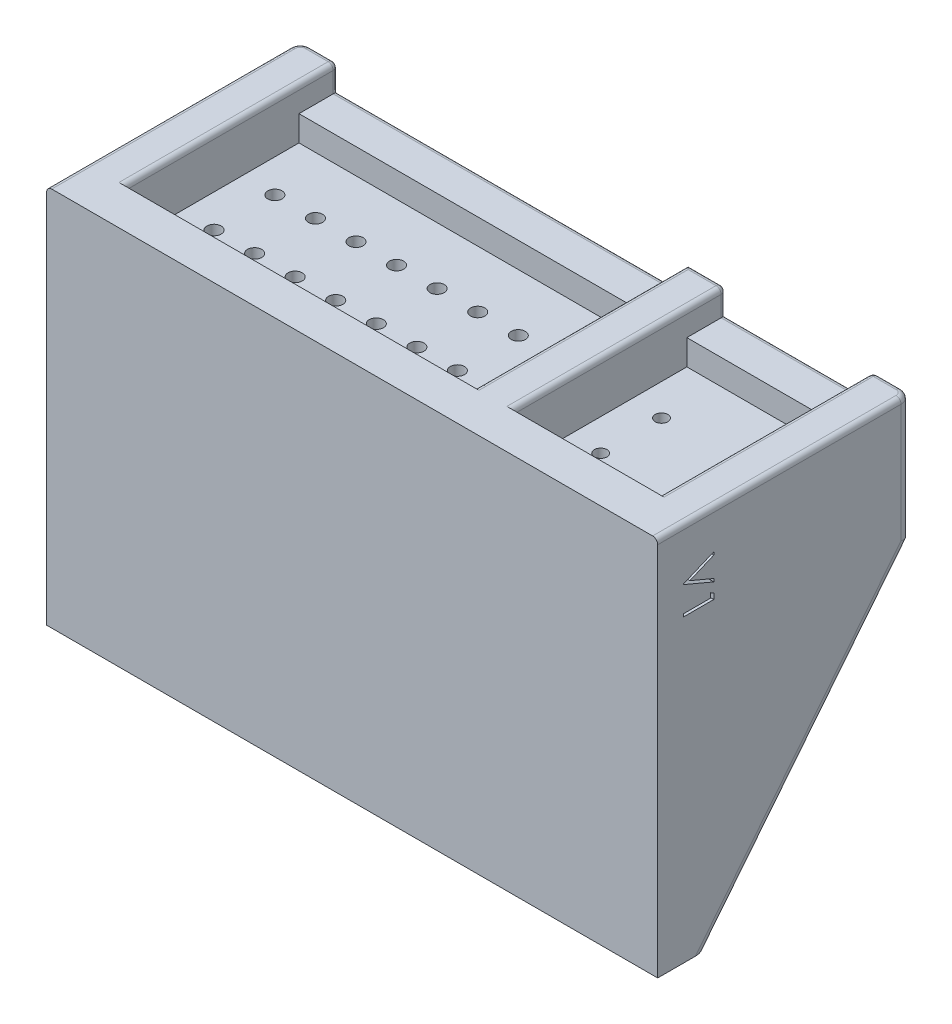
SolidWorks part; units mm, degrees
ref_plane "Front Plane" through (0, 0, 0) normal (0, 0, 1) x (1, 0, 0)
ref_plane "Top Plane" through (0, 0, 0) normal (0, 1, 0) x (1, 0, 0)
ref_plane "Right Plane" through (0, 0, 0) normal (1, 0, 0) x (0, 0, -1)
sketch "Sketch1" plane through (0, 0, 0) normal (0, 1, 0) x (1, 0, 0)
  line L1 (-60.25, -25) -> (60.25, -25)
  line L2 (-60.25, -25) -> (-60.25, 25)
  line L3 (-60.25, 25) -> (60.25, 25)
  line L4 (60.25, -25) -> (60.25, 25)
  line L5 (-60.25, -25) -> (60.25, 25) construction
  line L6 (-60.25, 25) -> (60.25, -25) construction
  point P0 (0, 0)
  dimension "D1" = 120.5
  dimension "D2" = 50
extrude "Boss-Extrude1" add sketch "Sketch1" along normal blind 25
sketch "Sketch2" plane through (0, 25, 0) normal (0, 1, 0) x (1, 0, 0)
  line L1 (23.75, -17.25) -> (52.75, -17.25)
  line L2 (23.75, -17.25) -> (23.75, 17.25)
  line L3 (23.75, 17.25) -> (52.75, 17.25)
  line L4 (52.75, -17.25) -> (52.75, 17.25)
  line L5 (23.75, -17.25) -> (52.75, 17.25) construction
  line L6 (23.75, 17.25) -> (52.75, -17.25) construction
  line L7 (60.25, -25) -> (60.25, 25) construction
  point P0 (38.25, 0)
  dimension "D1" = 34.5
  dimension "D2" = 29
  dimension "D3" = 7.5
extrude "Cut-Extrude1" cut sketch "Sketch2" against normal blind 10
sketch "Sketch3" plane through (0, 25, 0) normal (0, 1, 0) x (1, 0, 0)
  line L0 (23.75, 17.25) -> (23.75, -17.25) construction
  line L1 (-52.75, -17.25) -> (16.25, -17.25)
  line L2 (-52.75, -17.25) -> (-52.75, 17.25)
  line L3 (-52.75, 17.25) -> (16.25, 17.25)
  line L4 (16.25, -17.25) -> (16.25, 17.25)
  line L5 (-52.75, -17.25) -> (16.25, 17.25) construction
  line L6 (-52.75, 17.25) -> (16.25, -17.25) construction
  point P0 (-18.25, 0)
  dimension "D1" = 7.5
  dimension "D2" = 69
  dimension "D3" = 34.5
extrude "Cut-Extrude2" cut sketch "Sketch3" against normal blind 10
sketch "Sketch5" plane through (0, 15, 0) normal (0, 1, 0) x (1, 0, 0)
  line L0 (-48.7346, 0) -> (32.4983, 0) construction
  line L2 (-46.25, 6) -> (-38.25, 6) construction
  line L4 (-52.75, 17.25) -> (16.25, -17.25) construction
  line L5 (16.25, 17.25) -> (-52.75, -17.25) construction
  line L6 (-18.25, 0) -> (-41.795, 0) construction
  line L7 (-18.25, 0) -> (-18.25, 11.1048) construction
  line L8 (-52.75, 17.25) -> (-52.75, -17.25) construction
  circle A19 centre (-46.25, 6) radius 1.4
  circle A20 centre (-38.25, 6) radius 1.4
  circle A21 centre (-30.25, 6) radius 1.4
  circle A22 centre (-22.25, 6) radius 1.4
  circle A23 centre (-14.25, 6) radius 1.4
  circle A24 centre (-6.25, 6) radius 1.4
  circle A25 centre (1.75, 6) radius 1.4
  circle A26 centre (9.75, 6) radius 1.4
  circle A27 centre (-38.25, -6) radius 1.4
  circle A28 centre (-30.25, -6) radius 1.4
  circle A29 centre (-22.25, -6) radius 1.4
  circle A30 centre (-14.25, -6) radius 1.4
  circle A31 centre (-6.25, -6) radius 1.4
  circle A32 centre (1.75, -6) radius 1.4
  circle A33 centre (9.75, -6) radius 1.4
  circle A34 centre (-46.25, -6) radius 1.4
  dimension "D6" = 8
  dimension "D7" = 2.8
  dimension "D4" = 28
  dimension "D1" = 6
  dimension "D2" = 0
  dimension "D3" = 2
extrude "Cut-Extrude4" cut sketch "Sketch5" against normal through all
sketch "Sketch6" plane through (0, 15, 0) normal (0, 1, 0) x (1, 0, 0)
  line L0 (30, 6) -> (46, 6) construction
  line L1 (46, 6) -> (46, -6) construction
  line L2 (46, -6) -> (30, -6) construction
  line L3 (30, -6) -> (30, 6) construction
  line L6 (23.75, 17.25) -> (52.75, -17.25) construction
  line L7 (52.75, -17.25) -> (52.75, 17.25) construction
  line L8 (52.75, -17.25) -> (52.75, 17.25) construction
  line L9 (52.75, 17.25) -> (23.75, -17.25) construction
  circle A0 centre (30, 6) radius 1.25
  circle A1 centre (46, 6) radius 1.25
  point P17 (38.25, 0)
  dimension "D5" = 2.5
  dimension "D6" = 2.5
  dimension "D1" = 6
  dimension "D3" = 16
  dimension "D4" = 12
extrude "Cut-Extrude5" cut sketch "Sketch6" against normal through all
mirror "Mirror3" about plane through (0, 0, 0) normal (0, 0, 1) of "Cut-Extrude5"
sketch "Sketch8" plane through (0, 25, 0) normal (0, 1, 0) x (1, 0, 0)
  line L0 (-52.75, 17.25) -> (16.25, 17.25)
  line L1 (16.25, 17.25) -> (16.25, 25)
  line L2 (60.25, 25) -> (-60.25, 25) construction
  line L3 (16.25, 25) -> (-52.75, 25)
  line L4 (-52.75, 25) -> (-52.75, 17.25)
  line L5 (23.75, 17.25) -> (52.75, 17.25)
  line L6 (52.75, 17.25) -> (52.75, 25)
  line L7 (52.75, 25) -> (23.75, 25)
  line L8 (23.75, 25) -> (23.75, 17.25)
extrude "Cut-Extrude7" cut sketch "Sketch8" against normal blind 5
fillet "Fillet1" radius 1 14 edges at (52.75, 22.5, -25) (-18.25, 20, -25) (38.25, 20, -25) (-52.75, 22.5, -25) (23.75, 22.5, -25) (16.25, 25, -3.875) (20, 25, -25) (23.75, 25, -3.875) (52.75, 25, -3.875) (56.5, 25, -25) (60.25, 25, 0) (-60.25, 25, 0) (-56.5, 25, -25) (-52.75, 25, -3.875)
sketch "Sketch9" plane through (0, 0, 0) normal (0, -1, 0) x (1, 0, 0)
  line L0 (-60.25, -25) -> (-60.25, 25) construction
  line L1 (60.25, 25) -> (-60.25, 25)
  line L2 (60.25, 25) -> (60.25, 15)
  line L3 (60.25, 15) -> (-60.25, 15)
  line L4 (-60.25, 25) -> (-60.25, 15)
  dimension "D1" = 10
extrude "Boss-Extrude2" add sketch "Sketch9" along normal blind 50
sketch "Sketch10" plane through (-60.25, 0, 0) normal (-1, 0, 0) x (0, 0, 1)
  line L0 (-25, 0) -> (15, -50)
  line L1 (15, -50) -> (15, 0)
  line L2 (15, 0) -> (-25, 0)
extrude "Boss-Extrude3" add sketch "Sketch10" against normal blind 10
mirror "Mirror4" about plane through (0, 0, 0) normal (1, 0, 0) of "Boss-Extrude3"
fillet "Fillet3" radius 2 8 edges at (-59.9571, 24.7071, -24.7071) (59.9571, 24.7071, -24.7071) (60.25, 12, -25) (-60.25, 12, -25) (-60.25, -25, -5) (60.25, -25, -5) (-50.25, -25, -5) (50.25, -25, -5)
sketch "Sketch11" plane through (0, 0, 0) normal (0, -1, 0) x (1, 0, 0)
  line L0 (50.25, 15) -> (50.25, -22.4388) construction
  line L1 (50.25, -12) -> (-50.25, -12)
  line L2 (50.25, -12) -> (50.25, 12)
  line L3 (50.25, 12) -> (-50.25, 12)
  line L4 (-50.25, -12) -> (-50.25, 12)
  line L5 (-50.25, 15) -> (-50.25, -22.4388) construction
  circle A0 centre (46, -6) radius 1.25 construction
  circle A1 centre (46, 6) radius 1.25 construction
  dimension "D1" = 6
  dimension "D2" = 6
extrude "Recess" cut sketch "Sketch11" against normal blind 2
sketch "Sketch12" plane through (60.25, 0, 0) normal (1, 0, 0) x (0, 0, -1)
  line L0 (-19.9408, 17.5839) -> (-19.9408, -4.1264) construction
  text T0 "V1" font "Century Gothic" height 6
extrude "Cut-Extrude9" cut sketch "Sketch12" against normal blind 2
